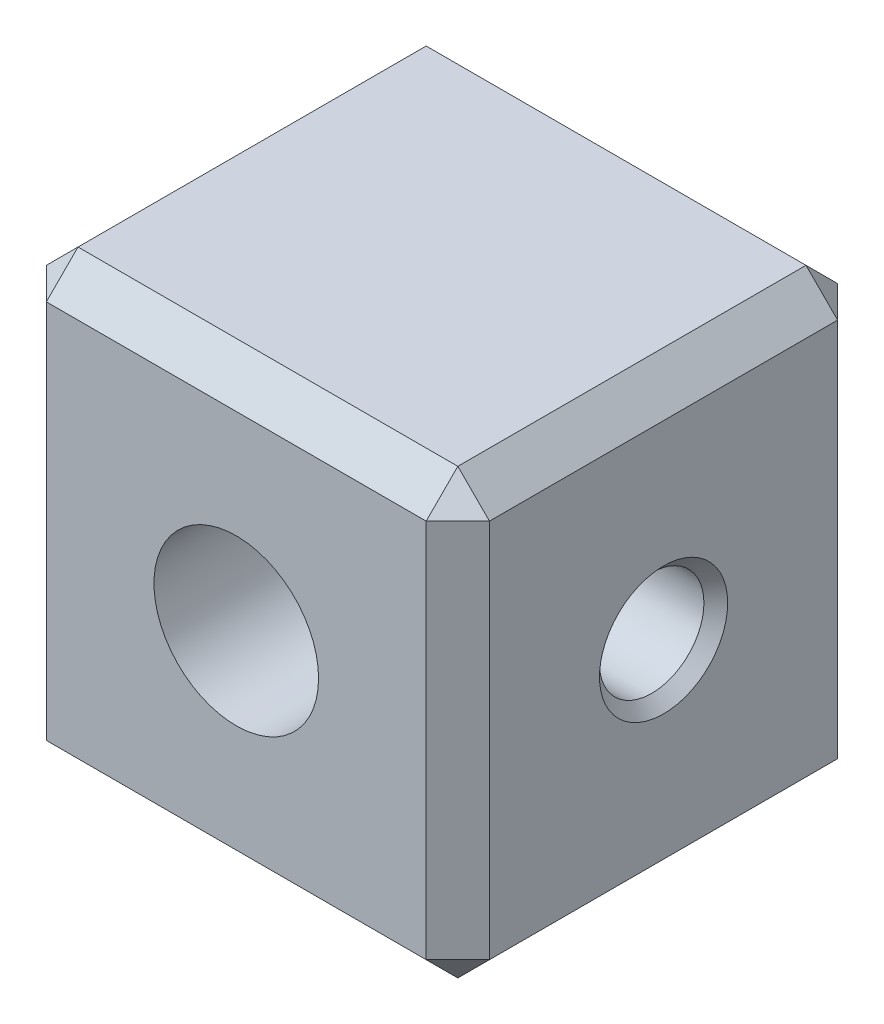
SolidWorks part; units mm, degrees
ref_plane "Front" through (0, 0, 0) normal (0, 0, 1) x (1, 0, 0)
ref_plane "Top" through (0, 0, 0) normal (0, 1, 0) x (1, 0, 0)
ref_plane "Right" through (0, 0, 0) normal (1, 0, 0) x (0, 0, -1)
sketch "Sketch1" plane through (0, 0, 0) normal (0, 0, 1) x (1, 0, 0)
  line L0 (-7, 0) -> (0, 0) construction
  line L1 (-7, 7) -> (7, 7)
  line L2 (-7, 7) -> (-7, -7)
  line L3 (-7, -7) -> (7, -7)
  line L4 (7, 7) -> (7, -7)
  line L5 (0, 0) -> (7, 0) construction
  circle A0 centre (0, 0) radius 2.6
  dimension "D2" = 5.2
  dimension "D1" = 14
extrude "Boss-Extrude1" add sketch "Sketch1" along normal blind 13
chamfer "Chamfer1" distance 1 angle 45 12 edges at (-7, -7, 6.5) (7, -7, 6.5) (-7, 7, 6.5) (7, 7, 6.5) (0, -7, 0) (-7, 0, 0) (0, 7, 0) (7, 0, 0) (0, -7, 13) (-7, 0, 13) (0, 7, 13) (7, 0, 13)
hole_wizard "M4 Tapped Hole1" positions "3DSketch1" profile "Sketch2" tap size "M4" standard "ISO" end condition up to next
sketch3d "3DSketch1"
  line L0 (7, -6, 6.5) -> (7, 0, 6.5) construction
  line L1 (7, -6, 12) -> (7, -6, 1) construction
  line L2 (7, 0, 6.5) -> (7, 6, 6.5) construction
  line L3 (7, 6, 1) -> (7, 6, 12) construction
  point P0 (7, 0, 6.5)
sketch "Sketch2" plane through (7, 0, 6.5) normal (0, 1, 0) x (0, 0, -1)
  line L0 (0, 0) -> (0, 4.4)
  line L1 (0, 4.4) -> (1.65, 4.4)
  line L2 (1.65, 4.4) -> (1.65, 0.375)
  line L3 (1.65, 0.375) -> (2.025, 0)
  line L5 (2.025, 0) -> (0, 0)
  line L6 (-1.65, 0.375) -> (-2.025, 0) construction
  line L11 (0, -6.35) -> (0, 107.95) construction
  dimension "Thread Major Dia." = 3.3
  dimension "Thru Tap Drill Depth" = 4.4
  dimension "Near C'Sink Dia." = 4.05
  dimension "Near C'Sink Angle" = 90
